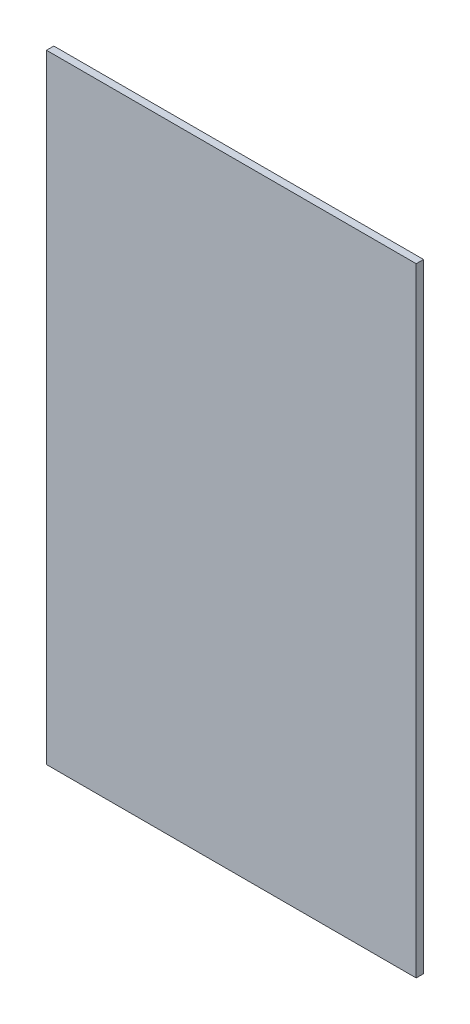
SolidWorks part; units mm, degrees
ref_plane "Front" through (0, 0, 0) normal (0, 0, 1) x (1, 0, 0)
ref_plane "Top" through (0, 0, 0) normal (0, 1, 0) x (1, 0, 0)
ref_plane "Right" through (0, 0, 0) normal (1, 0, 0) x (0, 0, -1)
sketch "Sketch1" plane through (0, 0, 0) normal (0, 0, 1) x (1, 0, 0)
  line L1 (0, 0) -> (302.4, 0)
  line L2 (0, 0) -> (0, 506)
  line L3 (0, 506) -> (302.4, 506)
  line L4 (302.4, 0) -> (302.4, 506)
  dimension "D1" = 302.4
  dimension "D2" = 506
extrude "Boss-Extrude1" add sketch "Sketch1" along normal blind 6
